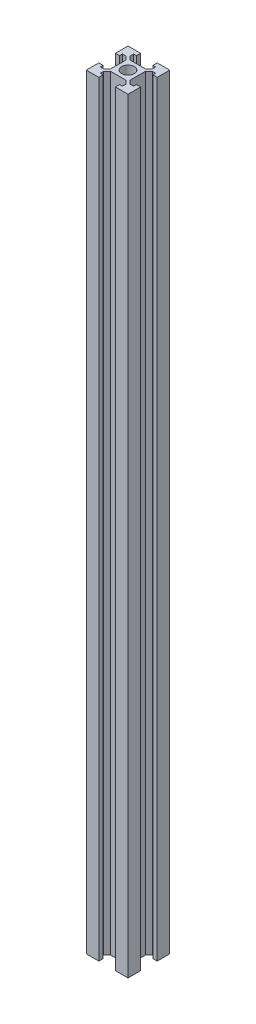
SolidWorks part; units mm, degrees
ref_plane "Front Plane" through (0, 0, 0) normal (0, 0, 1) x (1, 0, 0)
ref_plane "Top Plane" through (0, 0, 0) normal (0, 1, 0) x (1, 0, 0)
ref_plane "Right Plane" through (0, 0, 0) normal (1, 0, 0) x (0, 0, -1)
sketch "Sketch1" plane through (0, 0, 0) normal (0, 1, 0) x (1, 0, 0)
  line L0 (-30, 0) -> (30, 0) construction
  line L3 (-30, 30) -> (-12, 30)
  line L5 (-30, -30) -> (30, 30) construction
  line L6 (-30, 30) -> (30, -30) construction
  line L7 (0, 30) -> (0, -30) construction
  line L8 (-30, 12) -> (-24, 12)
  line L13 (-24, -24) -> (24, 24) construction
  line L14 (-24, 24) -> (24, -24) construction
  line L15 (-14, 24) -> (-14, 16) construction
  line L16 (-24, 16) -> (-19, 16)
  line L17 (-19, 16) -> (-14, 11)
  line L18 (-30, 12) -> (-30, 30)
  line L19 (-14, 11) -> (-14, -11)
  line L20 (-24, 12) -> (-24, 16)
  line L21 (-11, 14) -> (11, 14)
  line L22 (-16, 19) -> (-11, 14)
  line L23 (-12, 24) -> (-16, 24)
  line L24 (-16, 24) -> (-16, 19)
  line L25 (-12, 30) -> (-12, 24)
  line L26 (12, 30) -> (30, 30)
  line L27 (12, 30) -> (12, 24)
  line L28 (12, 24) -> (16, 24)
  line L29 (16, 24) -> (16, 19)
  line L30 (16, 19) -> (11, 14)
  line L31 (14, 11) -> (14, -11)
  line L32 (19, 16) -> (14, 11)
  line L33 (24, 12) -> (24, 16)
  line L34 (24, 16) -> (19, 16)
  line L35 (30, 12) -> (24, 12)
  line L36 (30, 12) -> (30, 30)
  line L37 (-14, -24) -> (-14, -16) construction
  line L38 (30, -12) -> (30, -30)
  line L39 (30, -12) -> (24, -12)
  line L40 (24, -16) -> (19, -16)
  line L41 (24, -12) -> (24, -16)
  line L42 (19, -16) -> (14, -11)
  line L43 (16, -19) -> (11, -14)
  line L44 (16, -24) -> (16, -19)
  line L45 (12, -24) -> (16, -24)
  line L46 (12, -30) -> (12, -24)
  line L47 (12, -30) -> (30, -30)
  line L48 (-12, -30) -> (-12, -24)
  line L49 (-16, -24) -> (-16, -19)
  line L50 (-12, -24) -> (-16, -24)
  line L51 (-16, -19) -> (-11, -14)
  line L52 (-11, -14) -> (11, -14)
  line L53 (-24, -12) -> (-24, -16)
  line L54 (-30, -12) -> (-30, -30)
  line L55 (-19, -16) -> (-14, -11)
  line L56 (-24, -16) -> (-19, -16)
  line L57 (-30, -12) -> (-24, -12)
  line L58 (-30, -30) -> (-12, -30)
  circle A0 centre (0, 0) radius 9
  point P0 (0, 0)
  point P10 (0, 0)
  point P34 (0, 14)
  point P41 (-14, 0)
  point P42 (14, 0)
  point P62 (0, -14)
  dimension "D1" = 18
  dimension "D3" = 12
  dimension "D5" = 16
  dimension "D6" = 5
  dimension "D7" = 5
  dimension "D8" = 6
extrude "Boss-Extrude1" add sketch "Sketch1" along normal blind 1100
